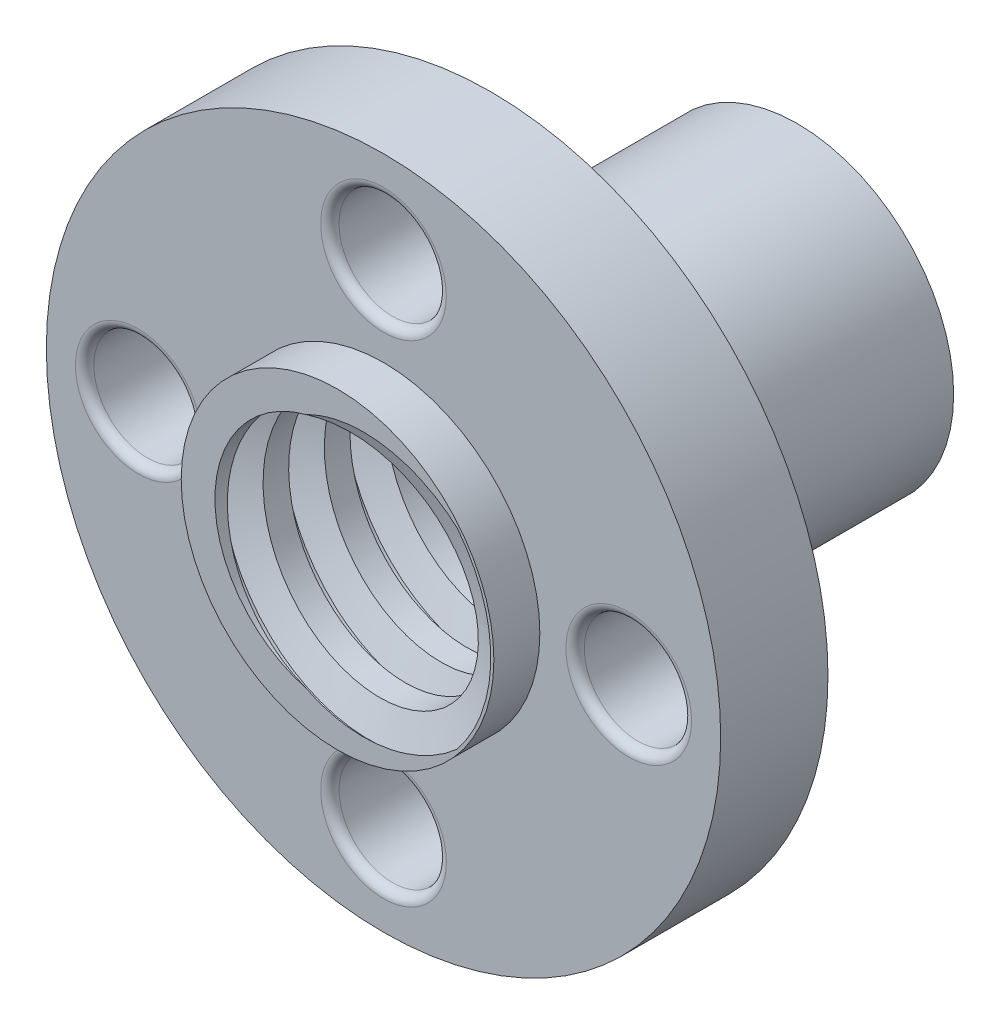
SolidWorks part; units mm, degrees
material "Brass"
ref_plane "Front Plane" through (0, 0, 0) normal (0, 0, 1) x (1, 0, 0)
ref_plane "Top Plane" through (0, 0, 0) normal (0, 1, 0) x (1, 0, 0)
ref_plane "Right Plane" through (0, 0, 0) normal (1, 0, 0) x (0, 0, -1)
sketch "Sketch1" plane through (0, 0, 0) normal (0, 0, 1) x (1, 0, 0)
  circle A0 centre (0, 0) radius 11
  circle A1 centre (0, 0) radius 5.1
  circle A2 centre (0, 0) radius 8 construction
  circle A3 centre (0, 8) radius 1.75
  circle A4 centre (8, 0) radius 1.75
  circle A5 centre (0, -8) radius 1.75
  circle A6 centre (-8, 0) radius 1.75
  point P16 (0, 0)
  dimension "D1" = 22
  dimension "D2" = 10.2
  dimension "D3" = 16
  dimension "D4" = 3.5
  dimension "D5" = 4
extrude "Boss-Extrude1" add sketch "Sketch1" against normal blind 3.5
sketch "Sketch2" plane through (0, 0, 0) normal (0, 0, 1) x (1, 0, 0)
  circle A0 centre (0, 0) radius 5.1
  circle A1 centre (0, 0) radius 4
  dimension "D1" = 8
  dimension "D2" = 10.2
extrude "Boss-Extrude2" add sketch "Sketch2" along normal blind 1.5 and the other way blind 13.5
sketch "Sketch3" plane through (0, 0, 1.5) normal (0, 0, 1) x (1, 0, 0)
  circle A0 centre (0, 0) radius 4
curve "Helix/Spiral1" pitch 2 height 15 radius 4 centre (0, 0, 1.5) axis (0, 0, -1) start towards (1, 0, 0)
sketch "Sketch4" plane through (0, 0, 0) normal (0, 1, 0) x (1, 0, 0)
  line L0 (3, -0.55) -> (3, -2.45)
  line L1 (3, -2.45) -> (5, -1.7146)
  line L2 (5, -1.7146) -> (5, -1.2854)
  line L3 (5, -1.2854) -> (3, -0.55)
  line L4 (3, -1.5) -> (5, -1.5)
  point P6 (4, -1.5)
  dimension "D1" = 1.9
  dimension "D2" = 2
  dimension "D3" = 69.811
sweep "Cut-Sweep1" cut profiles "Sketch4" path "Helix/Spiral1" align with end faces yes
fillet "Fillet2" radius 0.3 4 edges at (9.75, 0, 0) (1.75, -8, 0) (-6.25, 0, 0) (1.75, 8, 0)
